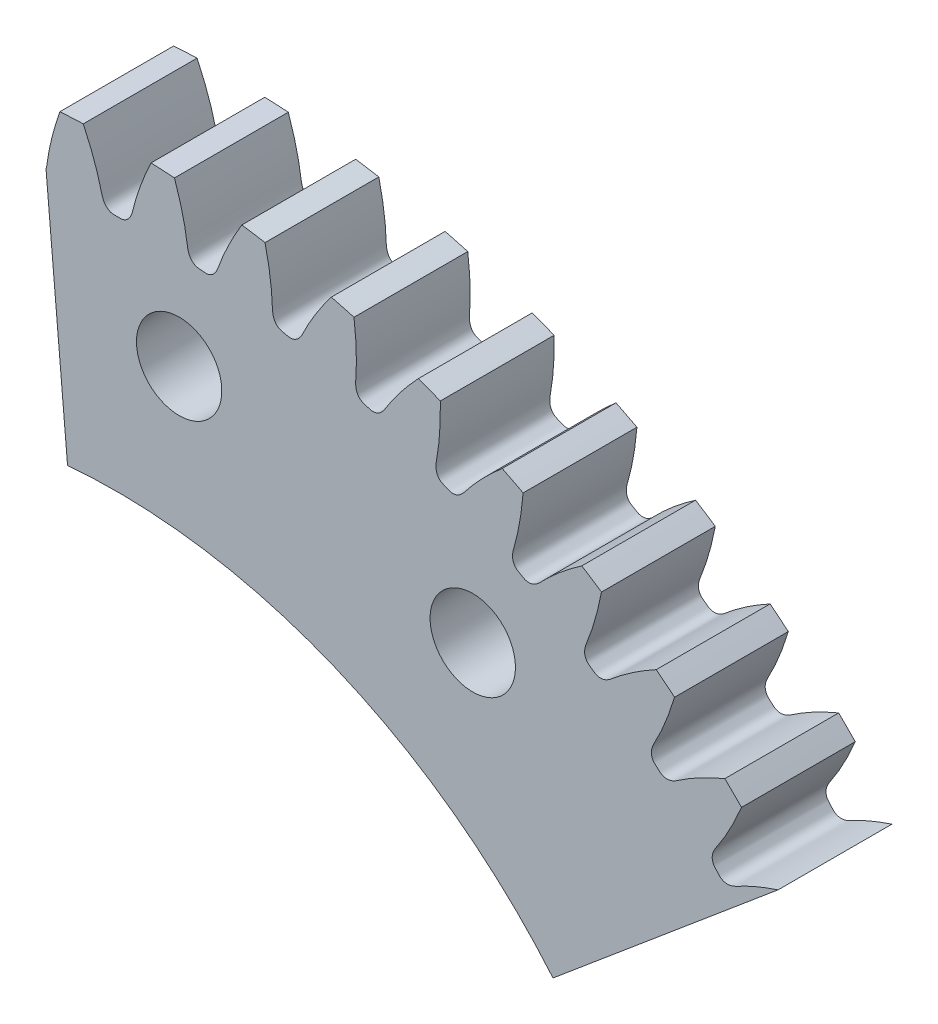
SolidWorks part; units mm, degrees
material "Д16 ГОСТ 4784-97"
ref_plane "FRONT" through (0, 0, 0) normal (0, 0, 1) x (1, 0, 0)
ref_plane "TOP" through (0, 0, 0) normal (0, 1, 0) x (1, 0, 0)
ref_plane "RIGHT" through (0, 0, 0) normal (1, 0, 0) x (0, 0, -1)
ref_axis "Ось1" through (0, 0, 50) along (0, 0, -1)
sketch "SketchRevolveSpurAssembly02Gear" plane through (0, 0, 0) normal (1, 0, 0) x (0, 0, -1)
  line L0 (0, 0) -> (1, 0) construction
  line L1 (-9.525, 0) -> (-9.525, 30.625)
  line L2 (-9.525, 30.625) -> (-5.525, 30.625)
  line L3 (-5.525, 30.625) -> (-5.525, 0)
  line L4 (-5.525, 0) -> (-9.525, 0)
  dimension "D1" = 4
revolve "SpurAssembly02Gear" add sketch "SketchRevolveSpurAssembly02Gear" angle 360 about L0
sketch "SketchToothSpurAssembly02Gear" plane through (0, 0, 0) normal (0, 0, 1) x (1, 0, 0)
  arc A0 (30.6326, 1.2046) -> (30.6326, -1.2046) centre (0, 0) cw
  spline S0 degree 3 poles (30.6326, -1.2046) (30.5439, -1.1625) (30.4122, -1.102) (30.2379, -1.0258) (30.1126, -0.973) (29.9907, -0.9234) (29.8725, -0.877) (29.7578, -0.8336) (29.6468, -0.7933) (29.5395, -0.7558) (29.4359, -0.721) (29.3362, -0.689) (29.2404, -0.6595) (29.1485, -0.6325) (29.0606, -0.6079) (28.9409, -0.5755) (28.8415, -0.5539) (28.7638, -0.5315) (28.7407, -0.5243) (28.7181, -0.5166) (28.6958, -0.5084) (28.6739, -0.4997) (28.6524, -0.4903) (28.6311, -0.4803) (28.61, -0.4694) (28.589, -0.4576) (28.5682, -0.4447) (28.5474, -0.4305) (28.5266, -0.4148) (28.5058, -0.3972) (28.4851, -0.3774) (28.4647, -0.355) (28.4448, -0.3295) (28.4259, -0.3007) (28.4086, -0.2682) (28.3939, -0.2321) (28.3828, -0.1925) (28.3763, -0.1527) (28.3733, -0.0882) (28.3763, 0) (28.3733, 0.0882) (28.3763, 0.1527) (28.3828, 0.1925) (28.3939, 0.2321) (28.4086, 0.2682) (28.4259, 0.3007) (28.4448, 0.3295) (28.4647, 0.355) (28.4851, 0.3774) (28.5058, 0.3972) (28.5266, 0.4148) (28.5474, 0.4305) (28.5682, 0.4447) (28.589, 0.4576) (28.61, 0.4694) (28.6311, 0.4803) (28.6524, 0.4903) (28.6739, 0.4997) (28.6958, 0.5084) (28.7181, 0.5166) (28.7407, 0.5243) (28.7638, 0.5315) (28.8415, 0.5539) (28.9409, 0.5755) (29.0606, 0.6079) (29.1485, 0.6325) (29.2404, 0.6595) (29.3362, 0.689) (29.4359, 0.721) (29.5395, 0.7558) (29.6468, 0.7933) (29.7578, 0.8336) (29.8725, 0.877) (29.9907, 0.9234) (30.1126, 0.973) (30.2379, 1.0258) (30.4122, 1.102) (30.5439, 1.1625) (30.6326, 1.2046) knots 0 0 0 0 0.054137 0.079973 0.104987 0.12918 0.15255 0.175099 0.196827 0.217732 0.237816 0.257078 0.275518 0.293137 0.309934 0.325909 0.361524 0.36604 0.370492 0.374889 0.379244 0.383572 0.387888 0.392212 0.396566 0.400977 0.405474 0.410093 0.414875 0.419864 0.425111 0.430667 0.436585 0.442907 0.44966 0.456842 0.464413 0.472285 0.479059 0.5 0.520941 0.527715 0.535587 0.543158 0.55034 0.557093 0.563415 0.569333 0.574889 0.580136 0.585125 0.589907 0.594526 0.599023 0.603434 0.607788 0.612112 0.616428 0.620756 0.625111 0.629508 0.63396 0.638476 0.674091 0.690066 0.706863 0.724482 0.742922 0.762184 0.782268 0.803173 0.824901 0.84745 0.87082 0.895013 0.920027 0.945863 1 1 1 1
extrude "ToothExtrudeCutSpurAssembly02Gear" cut sketch "SketchToothSpurAssembly02Gear" against normal blind 9.525 and the other way blind 9.525
pattern_circular "PatternSpurAssembly02Gear" count 60 every 6 about axis through (0, 0, 50) along (0, 0, -1) of "ToothExtrudeCutSpurAssembly02Gear"
sketch "AuxiliarySketchSpurAssembly02Gear" plane through (0, 0, 0) normal (0, 0, 1) x (1, 0, 0)
  circle A0 centre (0, 0) radius 30 construction
  circle A1 centre (0, 0) radius 28.1908 construction
  circle A2 centre (0, 0) radius 28.8404 construction
  circle A3 centre (0, 0) radius 30.625 construction
  circle A4 centre (0, 0) radius 28.375 construction
  dimension "PitchDiameter" = 60
  dimension "BaseDiameter" = 56.3816
  dimension "FormDiameter" = 57.6807
  dimension "MajorDiameter" = 61.25
  dimension "MinorDiameter" = 56.75
sketch "Эскиз1" plane through (0, 0, 5.525) normal (0, 0, -1) x (-1, 0, 0)
  line L0 (0, 0) -> (0, 37.9912) construction
  line L1 (0, 0) -> (-26.901, 26.901) construction
  line L2 (0, 0) -> (0.4358, 4.981) construction
  line L3 (0, 0) -> (-26.8116, 22.4976) construction
  line L4 (0, 0) -> (3.0505, 34.8668) construction
  line L5 (-15.3209, 12.8558) -> (-26.8116, 22.4976)
  line L6 (1.7431, 19.9239) -> (3.0505, 34.8668)
  line L7 (0, 0) -> (-8.054, 25.5439) construction
  line L8 (0, 0) -> (-2.3704, 27.0941) construction
  arc A0 (3.0505, 34.8668) -> (-26.8116, 22.4976) centre (0, 0) cw
  arc A1 (1.7431, 19.9239) -> (-15.3209, 12.8558) centre (0, 0) ccw
  arc A2 (2.1789, 24.9049) -> (-19.1511, 16.0697) centre (0, 0) ccw construction
  circle A3 centre (-2.1789, 24.9049) radius 1.5
  circle A4 centre (-12.5, 21.6506) radius 1.5
  dimension "D4" = 35
  dimension "D5" = 20
  dimension "D6" = 25
  dimension "D9" = 3
  dimension "D1" = 45
  dimension "D2" = 5
  dimension "D3" = 5
  dimension "D7" = 10
  dimension "D8" = 22.5
extrude "Вырез-Вытянуть1" cut sketch "Эскиз1" against normal through all
